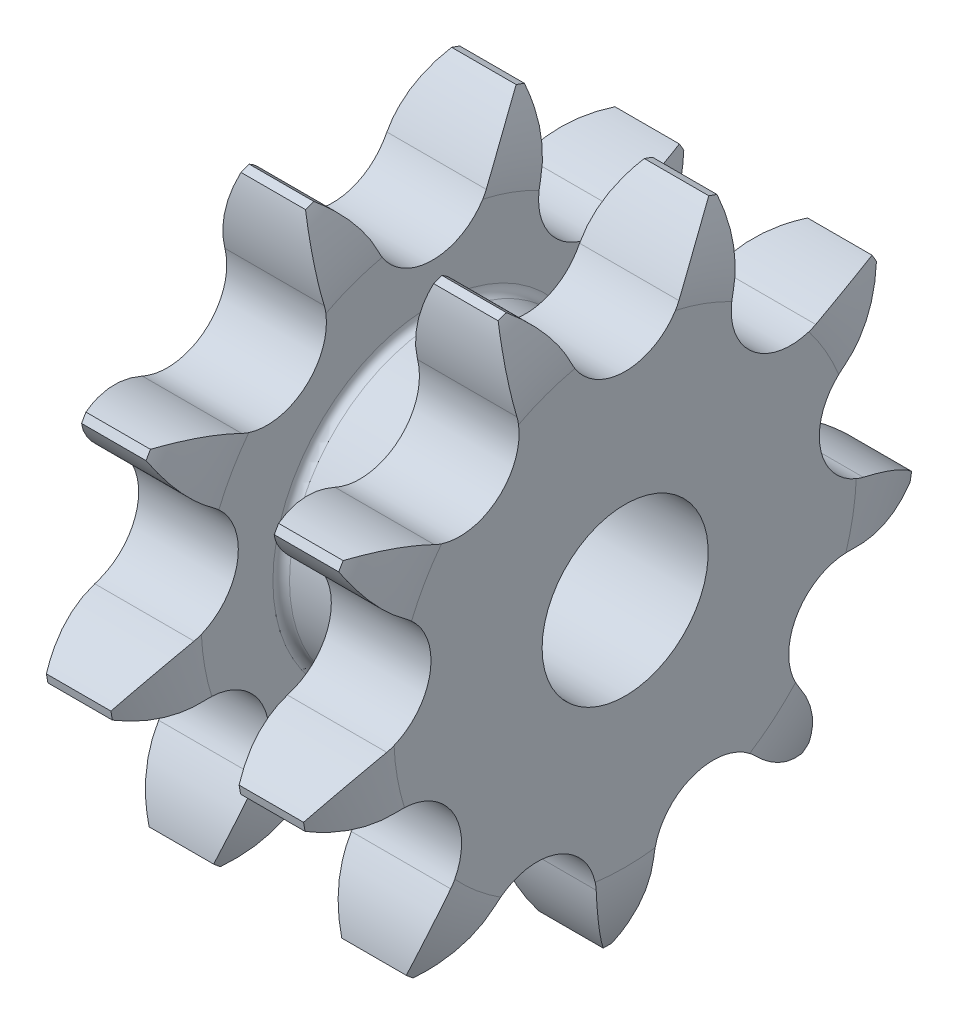
SolidWorks part; units mm, degrees
ref_plane "Plane1" through (0, 0, 0) normal (0, 0, 1) x (1, 0, 0)
ref_plane "Plane2" through (0, 0, 0) normal (0, 1, 0) x (1, 0, 0)
ref_plane "Plane3" through (0, 0, 0) normal (1, 0, 0) x (0, 0, -1)
sketch "Clipboard" plane through (0, 0, 0) normal (0, 1, 0) x (1, 0, 0)
  line L0 (0, 0) -> (12.5436, -1.9867)
  line L1 (-15, 0) -> (100, 0) construction
  line L2 (0, 0) -> (-0.8416, 0.9512)
  line L3 (0, 0) -> (-11.863, 4.5341)
  line L4 (0, 0) -> (3.0618, 0.4849)
  line L5 (0, 0) -> (-2.8109, -1.0484)
  line L6 (0, 0) -> (-17.5077, -11.8125)
  line L7 (-0.8416, 0.9512) -> (22.0505, 5.4009)
  line L8 (-76.2, 38.1) -> (-75.2, 38.1)
  line L9 (-73.4259, 41.6592) -> (-72.8306, 41.7344)
  line L10 (-73.4741, 12.7512) -> (-59.5541, 12.7512)
  circle A0 centre (0, 0) radius 4.255
  circle A1 centre (0, 0) radius 10.9305
  circle A2 centre (0, 0) radius 25
  dimension "Num_teeth" = 9
  dimension "Thickness" = 21.12
  dimension "Fillet_rad" = 0.6
sketch "BasProSke" plane through (0, 0, 0) normal (0, 1, 0) x (1, 0, 0)
  line L0 (-10, 0) -> (60, 0) construction
  line L1 (0, 0) -> (0, 16.7129)
  line L2 (0, 0) -> (21.12, 0)
  line L3 (21.12, 0) -> (21.12, 16.7129)
  line L4 (19.85, 22.2487) -> (1.27, 22.2487)
  arc A0 (0, 16.7129) -> (1.27, 22.2487) centre (12.7, 16.7129) cw
  arc A1 (21.12, 16.7129) -> (19.85, 22.2487) centre (8.42, 16.7129) ccw
  dimension "D1" = 12.7
  dimension "Thickness" = 21.12
  dimension "Diameter" = 44.4973
  dimension "G1" = 1.27
revolve "Base-Revolve" add sketch "BasProSke" angle 360 about L0
sketch "GrvSke" plane through (0, 0, 0) normal (0, 1, 0) x (1, 0, 0)
  line L0 (7.2, 16.7129) -> (7.2, 11.5305)
  line L1 (7.8, 10.9305) -> (13.32, 10.9305)
  line L2 (13.92, 11.5305) -> (13.92, 16.7129)
  line L3 (5.93, 22.2487) -> (15.19, 22.2487)
  line L4 (10.56, 0) -> (10.56, 52.07) construction
  line L5 (-10, 0) -> (60, 0) construction
  line L6 (0, 0) -> (35.56, 0) construction
  arc A0 (13.92, 16.7129) -> (15.19, 22.2487) centre (26.62, 16.7129) cw
  arc A1 (7.2, 16.7129) -> (5.93, 22.2487) centre (-5.5, 16.7129) ccw
  arc A2 (7.2, 11.5305) -> (7.8, 10.9305) centre (7.8, 11.5305) ccw
  arc A3 (13.32, 10.9305) -> (13.92, 11.5305) centre (13.32, 11.5305) ccw
  dimension "D1" = 12.7
  dimension "Diameter" = 44.4973
  dimension "Fillet_rad" = 0.6
  dimension "G1" = 1.27
  dimension "Grv_width" = 6.72
revolve "Groove" cut sketch "GrvSke" angle 360 about L6
sketch "TooCutSke" plane through (0, 0, 0) normal (1, 0, 0) x (0, 0, -1)
  line L0 (0, 18.6087) -> (3.8949, 16.7925) construction
  line L1 (0, 0) -> (0, 107) construction
  line L2 (0, 18.6087) -> (-10, 18.6087) construction
  line L3 (0, 18.6087) -> (-3.8949, 16.7925) construction
  arc A0 (3.8949, 16.7925) -> (7.8075, 21.3669) centre (14.0756, 12.0451) cw
  arc A1 (3.8949, 16.7925) -> (-3.8949, 16.7925) centre (0, 18.6087) cw
  arc A2 (-3.8949, 16.7925) -> (-7.8075, 21.3669) centre (-14.0756, 12.0451) ccw
  arc A3 (7.8075, 21.3669) -> (-7.8075, 21.3669) centre (0, 0) ccw
extrude "ToothCut" cut sketch "TooCutSke" along normal through all
pattern_circular "TeethCuts" count 9 every 40 about axis through (-10, 0, 0) along (1, 0, 0) of "ToothCut"
sketch "HubNeaOneSke" plane through (0, 0, 0) normal (-1, 0, 0) x (0, 0, 1)
  circle A0 centre (0, 0) radius 10.9305
  dimension "Diameter" = 21.861
extrude "HubNearOne" [suppressed] add sketch "HubNeaOneSke" along normal blind 2.2005
fillet "HubNearOneFillet" [suppressed] radius 0.6
sketch "HubNeaBotSke" plane through (0, 0, 0) normal (-1, 0, 0) x (0, 0, 1)
  circle A0 centre (0, 0) radius 10.9305
  dimension "Diameter" = 21.861
extrude "HubNearBoth" [suppressed] add sketch "HubNeaBotSke" along normal blind 1.1003
fillet "HubNearBothFillet" [suppressed] radius 0.6
ref_plane "FarPln" through (21.12, 0, 0) normal (1, 0, 0) x (0, 0, -1)
sketch "HubFarSke" plane through (21.12, 0, 0) normal (1, 0, 0) x (0, 0, -1)
  circle A0 centre (0, 0) radius 10.9305
  dimension "Diameter" = 21.861
extrude "HubFar" [suppressed] add sketch "HubFarSke" along normal blind 1.1003
fillet "HubFarFillet" [suppressed] radius 0.6
sketch "BorSke" plane through (0, 0, 0) normal (1, 0, 0) x (0, 0, -1)
  circle A0 centre (0, 0) radius 6
  dimension "Diameter" = 12
extrude "Bore" cut sketch "BorSke" along normal mid plane 46.641
sketch "KeySke" plane through (0, 0, 0) normal (1, 0, 0) x (0, 0, -1)
  line L0 (-1, 0) -> (-1, 7)
  line L1 (-1, 7) -> (1, 7)
  line L2 (1, 7) -> (1, 0)
  line L3 (0, 0) -> (0, 34) construction
  line L4 (-1, 0) -> (1, 0)
  dimension "Offset" = 7
  dimension "Width" = 2
extrude "Keyway" [suppressed] cut sketch "KeySke" along normal mid plane 46.641
pattern_circular "Keyway2" [suppressed] count 2 every 90 about axis through (-10, 0, 0) along (1, 0, 0)
equation "' \"Pitch@Clipboard\" = 12.7"
equation "' \"Num_strands@Clipboard\" = 2"
equation "' \"Num_teeth@Clipboard\" = 9"
equation "' \"Hub_dia@Clipboard\" = 50"
equation "' \"Overall_len@Clipboard\" = 3"
equation "' \"Diameter@BorSke\" = 12"
equation "' \"T_dim@Clipboard\" = 1"
equation "' \"Width@KeySke\" = 2"
equation "' \"Dr@Clipboard\" = 8.51"
equation "' \"Face_width@Clipboard\" = 7.2"
equation "' \"Side_radius@Clipboard\" = 12.7"
equation "' \"Side_relief@Clipboard\" = 1.27"
equation "' \"Transv_pitch@Clipboard\" = 13.92"
equation "' \"Show_teeth@Clipboard\" = 9"
equation "' \"Fillet_rad@Clipboard\" = 0.6"
equation "' \"Plate_wid@Clipboard\" = 11.8"
equation "\"Num_teeth@Clipboard\" = int( \"Num_teeth@Clipboard\" )"
equation "\"Num_teeth@Clipboard\" = ((sgn( \"Num_teeth@Clipboard\" - 5.0)+1)*( \"Num_teeth@Clipboard\" - 5.0))/2 +5.0"
equation "\"Num_teeth@Clipboard\" = ((sgn( \"Num_teeth@Clipboard\" - 200.0)-1)*( \"Num_teeth@Clipboard\" - 200.0))/-2 +200.0"
equation "\"MHD@Clipboard\" = \"Pitch@Clipboard\" * (1.0 / tan(3.14159265 / \"Num_teeth@Clipboard\" )) - 1.04 * \"Plate_wid@Clipboard\" - 0.76"
equation "\"Thickness@Clipboard\"  = \"Face_width@Clipboard\" + (\"Num_strands@Clipboard\" - 1) * \"Transv_pitch@Clipboard\""
equation "\"OAL@Clipboard\" = \"Thickness@Clipboard\" + 2 * \"Fillet_rad@Clipboard\" + 1"
equation "\"MHD@Clipboard\" = ((sgn( \"MHD@Clipboard\" - \"Hub_dia@Clipboard\" )-1)*( \"MHD@Clipboard\" - \"Hub_dia@Clipboard\" ))/-2+ \"Hub_dia@Clipboard\""
equation "\"OAL@Clipboard\" = ((sgn( \"OAL@Clipboard\" - \"Overall_len@Clipboard\" )+1)*( \"OAL@Clipboard\" - \"Overall_len@Clipboard\" ))/2 + \"Overall_len@Clipboard\" + 0.0005"
equation "\"Num_teeth@TeethCuts\" = int( \"Show_teeth@Clipboard\" ) + 1"
equation "\"Num_teeth@TeethCuts\" = ((sgn( \"Num_teeth@TeethCuts\" - \"Num_teeth@Clipboard\" )-1)*( \"Num_teeth@TeethCuts\" - \"Num_teeth@Clipboard\" ))/-2+ \"Num_teeth@Clipboard\""
equation "\"Num_teeth@TeethCuts\" = ((sgn( \"Num_teeth@TeethCuts\" - 2.0)+1)*( \"Num_teeth@TeethCuts\" - 2.0))/2 +2.0"
equation "\"Angle@TeethCuts\" = 360.0 / \"Num_teeth@Clipboard\""
equation "\"Seat_radius@TooCutSke\" = ( \"Pitch@Clipboard\" / 2.0) / sin(3.14159265 / \"Num_teeth@Clipboard\" ) - \"Dr@Clipboard\" / 2.0 + \"Dr@Clipboard\" * 0.505"
equation "\"R1@TooCutSke\"  = \"Dr@Clipboard\" * 0.505"
equation "\"X@TooCutSke\" = 140.0 - (90.0 / \"Num_teeth@Clipboard\")"
equation "\"R2@TooCutSke\" = 0.12 * \"Dr@Clipboard\" * ( \"Num_teeth@Clipboard\" + 2.0)"
equation "\"Overcut@TooCutSke\" = 0.5 + 0.625 * \"Pitch@Clipboard\" - 0.5 * \"Dr@Clipboard\"  +  \"Pitch@Clipboard\" / 2.0 / sin(3.14159265 / \"Num_teeth@Clipboard\" )"
equation "\"Diameter@BasProSke\" = 2.0 * ( 0.625 * \"Pitch@Clipboard\" - 0.5 * \"Dr@Clipboard\"  +  \"Pitch@Clipboard\" / 2.0 / sin(3.14159265 / \"Num_teeth@Clipboard\" ))"
equation "\"Thickness@BasProSke\"  = \"Thickness@Clipboard\""
equation "\"G1@BasProSke\" =  \"Side_relief@Clipboard\""
equation "\"G2@BasProSke\" =  \"Side_relief@Clipboard\""
equation "\"D1@BasProSke\" =  \"Side_radius@Clipboard\""
equation "\"Diameter@GrvSke\" = \"Diameter@BasProSke\""
equation "\"G1@GrvSke\" = \"Side_relief@Clipboard\""
equation "\"D1@GrvSke\" = \"Side_radius@Clipboard\""
equation "\"Grv_diam@GrvSke\" =  \"Pitch@Clipboard\" * (1.0 / tan(3.14159265 / \"Num_teeth@Clipboard\" ))- 1.04 * \"Plate_wid@Clipboard\" - 0.76"
equation "\"Grv_width@GrvSke\" =  \"Transv_pitch@Clipboard\" - \"Face_width@Clipboard\""
equation "\"Offset@GrvSke\" = \"Grv_width@GrvSke\" / 2.0 + \"Face_width@Clipboard\""
equation "\"Fillet_rad@GrvSke\" = \"Fillet_rad@Clipboard\""
equation "\"Diameter@HubNeaOneSke\" = \"MHD@Clipboard\""
equation "\"Length@HubNearOne\" = \"OAL@Clipboard\" - \"Thickness@BasProSke\""
equation "\"Diameter@HubNeaBotSke\" = \"MHD@Clipboard\""
equation "\"Length@HubNearBoth\" = ( \"OAL@Clipboard\" - \"Thickness@BasProSke\" ) / 2.0"
equation "\"D1@HubNearOneFillet\" = \"Fillet_rad@Clipboard\""
equation "\"D1@HubNearBothFillet\" = \"Fillet_rad@Clipboard\""
equation "\"Thickness@FarPln\" = \"Thickness@BasProSke\""
equation "\"Diameter@HubFarSke\" = \"MHD@Clipboard\""
equation "\"Length@HubFar\" = ( \"OAL@Clipboard\" - \"Thickness@BasProSke\" ) / 2.0"
equation "\"D1@HubFarFillet\" = \"Fillet_rad@Clipboard\""
equation "\"D1@Bore\" = \"OAL@Clipboard\" * 2.0"
equation "\"D1@Keyway\" = \"OAL@Clipboard\" * 2.0"
equation "\"Offset@KeySke\" = \"T_dim@Clipboard\" + \"Diameter@BorSke\" / 2.0"
